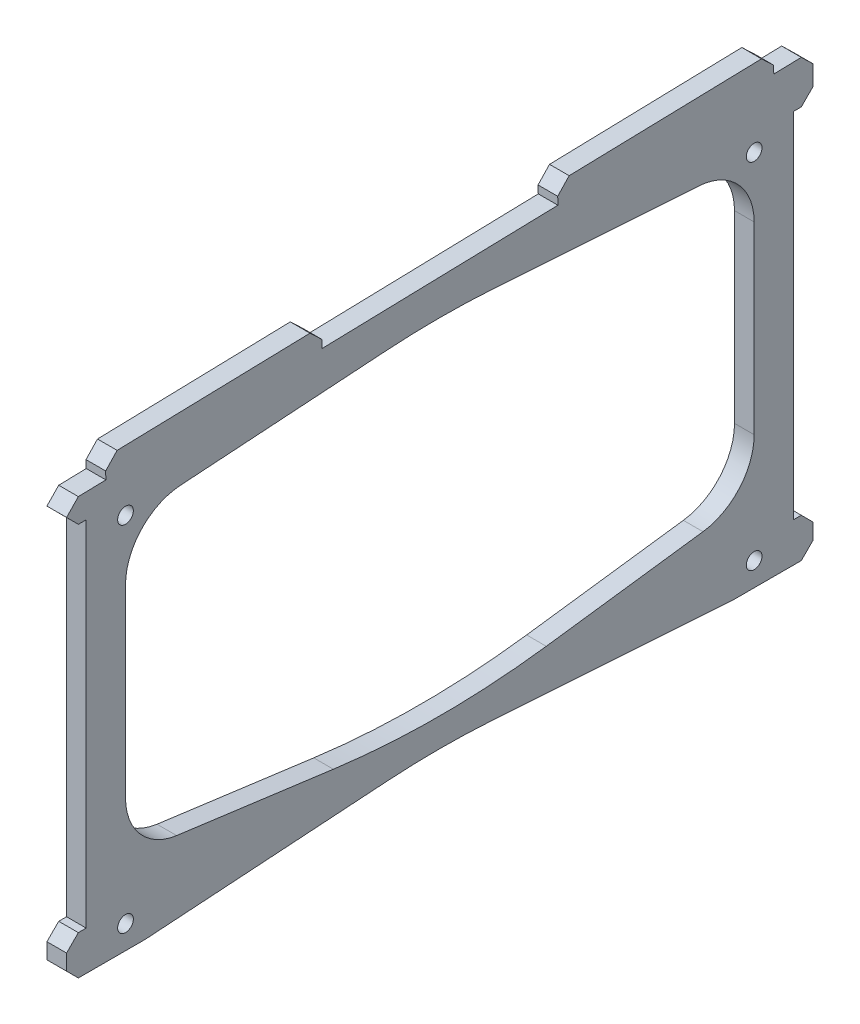
SolidWorks part; units mm, degrees
material "Stal węglowa"
ref_plane "Front" through (0, 0, 0) normal (0, 0, 1) x (1, 0, 0)
ref_plane "Top" through (0, 0, 0) normal (0, 1, 0) x (1, 0, 0)
ref_plane "Right" through (0, 0, 0) normal (1, 0, 0) x (0, 0, -1)
sketch "Szkic1" plane through (0, 0, 0) normal (1, 0, 0) x (0, 0, -1)
  line L78 (-432.3919, 109.7036) -> (-432.4443, 111.7029)
  line L79 (-439.3919, 103.4111) -> (-437.3919, 103.4111)
  line L80 (-252.3919, 106.4111) -> (-252.3919, 111.4171)
  line L81 (-252.3919, 6.4111) -> (-252.3919, 10.4111)
  line L82 (-437.3919, 13.4111) -> (-437.3919, 103.4111)
  line L83 (-255.3919, 13.4111) -> (-257.3919, 13.4111)
  line L84 (-255.3919, 103.4111) -> (-257.3919, 103.4111)
  line L85 (-257.3919, 13.4111) -> (-257.3919, 103.4111)
  line L86 (-422.3919, 3.4111) -> (-360.6957, 7.5242)
  line L87 (-262.3919, 114.1552) -> (-262.4443, 116.1545)
  line L88 (-272.3919, 3.4111) -> (-334.0881, 7.5242)
  line L89 (-255.3919, 3.4111) -> (-272.3919, 3.4111)
  line L90 (-380.4461, 116.0656) -> (-429.5239, 114.7804)
  line L91 (-317.3892, 114.7166) -> (-317.3368, 112.7156)
  line L92 (-265.5218, 119.075) -> (-314.4687, 117.7933)
  line L93 (-377.3162, 111.145) -> (-317.3368, 112.7156)
  line L94 (-377.3686, 113.1451) -> (-377.3162, 111.145)
  line L95 (-442.3919, 6.4111) -> (-442.3919, 10.4111)
  line L96 (-439.3919, 13.4111) -> (-437.3919, 13.4111)
  line L97 (-439.3919, 3.4111) -> (-422.3919, 3.4111)
  line L98 (-432.3919, 109.7036) -> (-439.393, 109.5203)
  line L99 (-255.3909, 114.3386) -> (-262.3919, 114.1552)
  line L100 (-427.3919, 37.1662) -> (-427.3919, 84.0556)
  line L101 (-320.2984, 16.9793) -> (-280.4095, 22.2978)
  line L102 (-374.4855, 16.9793) -> (-414.3744, 22.2978)
  line L103 (-361.0283, 102.5131) -> (-413.3897, 99.0223)
  line L104 (-267.3919, 37.1662) -> (-267.3919, 84.0556)
  line L105 (-333.7555, 102.5131) -> (-281.3942, 99.0223)
  line L106 (-432.4443, 111.7029) -> (-429.5239, 114.7804)
  line L107 (-442.3919, 10.4111) -> (-439.3919, 13.4111)
  line L108 (-442.3919, 106.4264) -> (-439.3919, 103.4111)
  line L109 (-439.393, 109.5203) -> (-442.3919, 106.4264)
  line L110 (-380.4461, 116.0656) -> (-377.3686, 113.1451)
  line L111 (-317.3892, 114.7166) -> (-314.4687, 117.7933)
  line L112 (-265.5218, 119.075) -> (-262.4443, 116.1545)
  line L113 (-255.3909, 114.3386) -> (-252.3919, 111.4171)
  line L114 (-252.3919, 106.4111) -> (-255.3919, 103.4111)
  line L115 (-255.3919, 13.4111) -> (-252.3919, 10.4111)
  line L116 (-252.3919, 6.4111) -> (-255.3919, 3.4111)
  line L117 (-442.3919, 6.4111) -> (-439.3919, 3.4111)
  arc A22 (-334.0881, 7.5242) -> (-360.6957, 7.5242) centre (-347.3919, -192.0329) ccw
  circle A23 centre (-267.3919, 9.4111) radius 2
  circle A24 centre (-267.3919, 99.4111) radius 2
  circle A25 centre (-427.3919, 9.4111) radius 2
  circle A26 centre (-427.3919, 99.4111) radius 2
  arc A27 (-413.3897, 99.0223) -> (-427.3919, 84.0556) centre (-412.3919, 84.0556) ccw
  arc A28 (-427.3919, 37.1662) -> (-414.3744, 22.2978) centre (-412.3919, 37.1662) ccw
  arc A29 (-374.4855, 16.9793) -> (-320.2984, 16.9793) centre (-347.3919, 220.181) ccw
  arc A30 (-267.3919, 84.0556) -> (-281.3942, 99.0223) centre (-282.3919, 84.0556) ccw
  arc A31 (-333.7555, 102.5131) -> (-361.0283, 102.5131) centre (-347.3919, -102.0329) ccw
  arc A32 (-280.4095, 22.2978) -> (-267.3919, 37.1662) centre (-282.3919, 37.1662) ccw
extrude "Dodanie-wyciągnięcie1" add sketch "Szkic1" along normal blind 5
